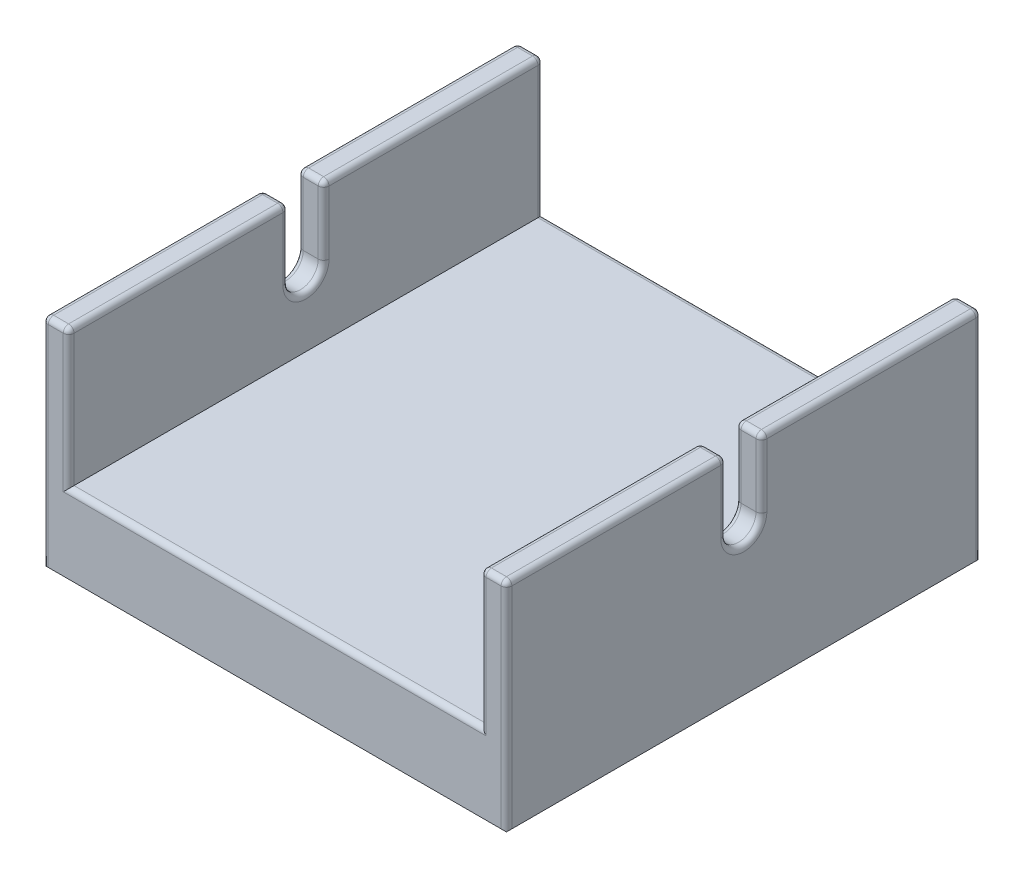
SolidWorks part; units mm, degrees
ref_plane "Front Plane" through (0, 0, 0) normal (0, 0, 1) x (1, 0, 0)
ref_plane "Top Plane" through (0, 0, 0) normal (0, 1, 0) x (1, 0, 0)
ref_plane "Right Plane" through (0, 0, 0) normal (1, 0, 0) x (0, 0, -1)
sketch "Sketch2" plane through (0, 34, 0) normal (0, -1, 0) x (-1, 0, 0)
  line L0 (-150, -197.8) -> (-150, 107) construction
  line L1 (-152.164, -197.8) -> (-147.836, -197.8) construction
  line L2 (-300, 107) -> (0, 107) construction
  line L4 (-107.1248, 0) -> (-192.8752, 0)
  line L5 (-107.1248, 0) -> (-107.1248, -87.8)
  line L6 (-107.1248, -87.8) -> (-192.8752, -87.8)
  line L7 (-192.8752, 0) -> (-192.8752, -87.8)
  line L8 (-107.1248, 0) -> (-192.8752, -87.8) construction
  line L9 (-107.1248, -87.8) -> (-192.8752, 0) construction
  line L10 (-300, 0) -> (0, 0) construction
  line L11 (-188.1, -87.8) -> (-188.1, 0)
  line L12 (-111.9, -87.8) -> (-111.9, 0)
  line L13 (-107.1248, -10) -> (-192.8752, -10)
  point P6 (-150, -43.9)
  dimension "D1" = 10
extrude "Boss-Extrude1" add sketch "Sketch2" along normal blind 15 contours L6 L7 L4 L5
extrude "Boss-Extrude2" add sketch "Sketch2<3>" against normal blind 25.4 contours L5 L13 L12 L6 | L13 L5 L4 L12 | L11 L13 L7 L6 | L13 L11 L4 L7 region at (109.5124, 34, 5) region at (109.5124, 34, 48.9) region at (190.4876, 34, 5) region at (190.4876, 34, 48.9)
sketch "Sketch2<3>" plane through (0, 34, 0) normal (0, -1, 0) x (-1, 0, 0) same geometry as "Sketch2"
sketch "Sketch3" plane through (192.8752, 0, 0) normal (1, 0, 0) x (0, 0, -1)
  line L0 (107, 46.7) -> (-87.8, 46.7) construction
  line L1 (107, 48.864) -> (107, 44.536) construction
  line L2 (-87.8, 19) -> (-87.8, 59.4) construction
  line L3 (-47.1639, 46.7) -> (-47.1639, 59.4)
  line L4 (-47.1639, 59.4) -> (-40.6361, 59.4)
  line L5 (-40.6361, 59.4) -> (-40.6361, 46.7)
  line L6 (0, 59.4) -> (-87.8, 59.4) construction
  line L7 (-47.1639, 59.4) -> (-87.8, 59.4) construction
  line L8 (-40.6361, 59.4) -> (0, 59.4) construction
  arc A0 (-40.6361, 46.7) -> (-47.1639, 46.7) centre (-43.9, 46.7) cw
  dimension "D1" = 3.2639
extrude "Cut-Extrude1" cut sketch "Sketch3" against normal through all
chamfer "Chamfer1" distance 0.5 angle 45 4 edges at (150, 19, 87.8) (192.8752, 19, 43.9) (150, 19, 0) (107.1248, 19, 43.9)
fillet "Fillet2" radius 1 38 edges at (111.9, 53.05, 40.6361) (111.9, 43.4361, 43.9) (107.1248, 53.05, 40.6361) (107.1248, 43.4361, 43.9) (192.8752, 53.05, 40.6361) (192.8752, 43.4361, 43.9) (188.1, 53.05, 40.6361) (188.1, 43.4361, 43.9) (109.5124, 59.4, 0) (111.9, 59.4, 20.3181) (109.5124, 59.4, 40.6361) (107.1248, 59.4, 20.3181) (109.5124, 59.4, 87.8) (107.1248, 59.4, 67.482) (111.9, 59.4, 67.482) (190.4876, 59.4, 0) (192.8752, 59.4, 20.3181) (190.4876, 59.4, 40.6361) (188.1, 59.4, 20.3181) (190.4876, 59.4, 87.8) (188.1, 59.4, 67.482) (192.8752, 59.4, 67.482) (111.9, 53.05, 47.1639) (109.5124, 59.4, 47.1639) (107.1248, 53.05, 47.1639) (192.8752, 53.05, 47.1639) (190.4876, 59.4, 47.1639) (188.1, 53.05, 47.1639) (150, 34, 87.8) (107.1248, 39.45, 87.8) (188.1, 46.7, 87.8) (111.9, 46.7, 87.8) (192.8752, 39.45, 87.8) (107.1248, 39.45, 0) (192.8752, 39.45, 0) (188.1, 46.7, 0) (150, 34, 0) (111.9, 46.7, 0)
